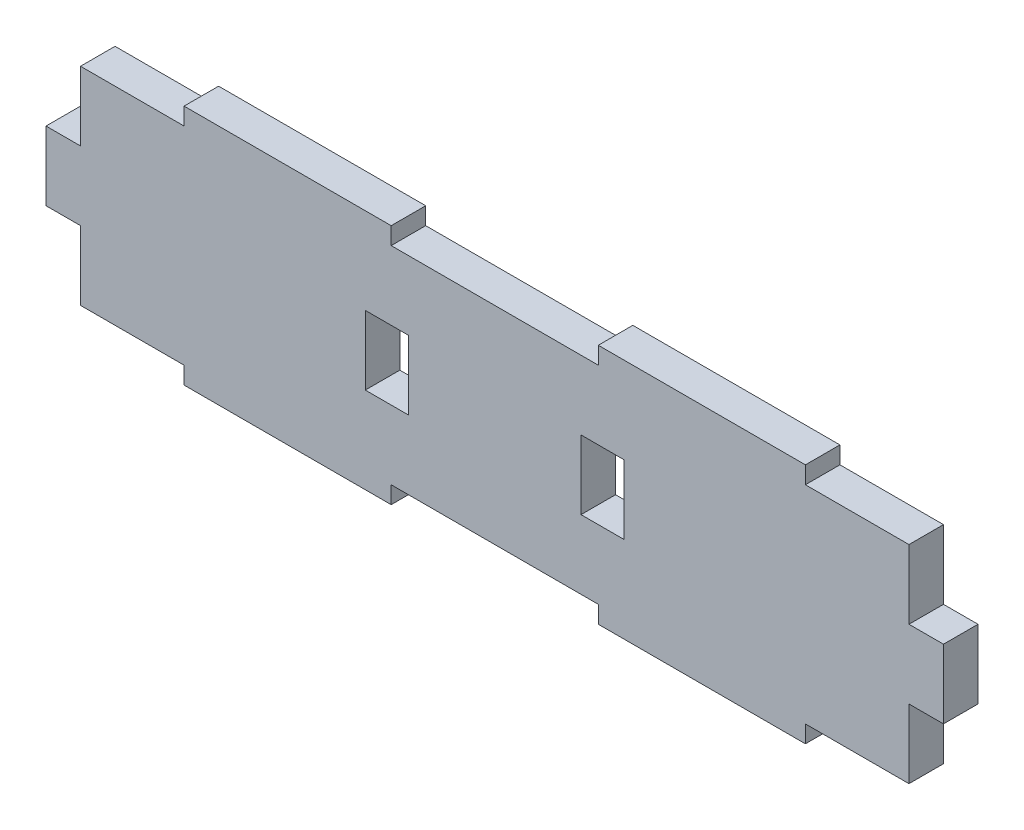
SolidWorks part; units mm, degrees
material "7050-T73510"
ref_plane "Front Plane" through (0, 0, 0) normal (0, 0, 1) x (1, 0, 0)
ref_plane "Top Plane" through (0, 0, 0) normal (0, 1, 0) x (1, 0, 0)
ref_plane "Right Plane" through (0, 0, 0) normal (1, 0, 0) x (0, 0, -1)
sketch "Sketch1" plane through (0, 0, 0) normal (0, 0, 1) x (1, 0, 0)
  line L1 (-165.1, -38.1) -> (165.1, -38.1)
  line L2 (-165.1, -38.1) -> (-165.1, 38.1)
  line L3 (-165.1, 38.1) -> (165.1, 38.1)
  line L4 (165.1, -38.1) -> (165.1, 38.1)
  line L5 (-165.1, -38.1) -> (165.1, 38.1) construction
  line L6 (-165.1, 38.1) -> (165.1, -38.1) construction
  point P0 (0, 0)
  dimension "D1" = 330.2
  dimension "D2" = 76.2
extrude "Boss-Extrude1" add sketch "Sketch1" along normal blind 12.7 contours L1 L3 region at (0, 0, 0)
sketch "Sketch2" plane through (0, 0, 12.7) normal (0, 0, 1) x (1, 0, 0)
  line L0 (-165.1, -38.1) -> (165.1, -38.1) construction
  line L1 (-38.1, -38.1) -> (-114.3, -38.1)
  line L2 (-38.1, -38.1) -> (-38.1, -44.45)
  line L3 (-38.1, -44.45) -> (-114.3, -44.45)
  line L4 (-114.3, -38.1) -> (-114.3, -44.45)
  line L5 (0, -55) -> (0, 55) construction
  line L6 (38.1, -44.45) -> (114.3, -44.45)
  line L7 (114.3, -38.1) -> (114.3, -44.45)
  line L8 (38.1, -38.1) -> (114.3, -38.1)
  line L9 (38.1, -38.1) -> (38.1, -44.45)
  line L10 (55, 0) -> (-55, 0) construction
  line L11 (38.1, 38.1) -> (38.1, 44.45)
  line L12 (38.1, 38.1) -> (114.3, 38.1)
  line L13 (114.3, 38.1) -> (114.3, 44.45)
  line L14 (38.1, 44.45) -> (114.3, 44.45)
  line L15 (-38.1, 44.45) -> (-114.3, 44.45)
  line L16 (-114.3, 38.1) -> (-114.3, 44.45)
  line L17 (-38.1, 38.1) -> (-114.3, 38.1)
  line L18 (-38.1, 38.1) -> (-38.1, 44.45)
  point P12 (-38.1, -41.275)
  dimension "D1" = 76.2
  dimension "D2" = 6.35
  dimension "D3" = 76.2
extrude "Boss-Extrude2" add sketch "Sketch2" against normal blind 12.7
sketch "Sketch3" plane through (0, 0, 12.7) normal (0, 0, 1) x (1, 0, 0)
  line L0 (6.985, 0) -> (-6.985, 0) construction
  line L1 (-165.1, -38.1) -> (-152.4, -38.1)
  line L2 (-165.1, -38.1) -> (-165.1, -12.7)
  line L3 (-165.1, -12.7) -> (-152.4, -12.7)
  line L4 (-152.4, -38.1) -> (-152.4, -12.7)
  line L6 (-165.1, 12.7) -> (-152.4, 12.7)
  line L7 (-152.4, 38.1) -> (-152.4, 12.7)
  line L8 (-165.1, 38.1) -> (-152.4, 38.1)
  line L9 (-165.1, 38.1) -> (-165.1, 12.7)
  line L10 (0, -6.985) -> (0, 6.985) construction
  line L11 (165.1, 38.1) -> (165.1, 12.7)
  line L12 (165.1, 38.1) -> (152.4, 38.1)
  line L13 (152.4, 38.1) -> (152.4, 12.7)
  line L14 (165.1, 12.7) -> (152.4, 12.7)
  line L15 (165.1, -12.7) -> (152.4, -12.7)
  line L16 (152.4, -38.1) -> (152.4, -12.7)
  line L17 (165.1, -38.1) -> (152.4, -38.1)
  line L18 (165.1, -38.1) -> (165.1, -12.7)
  line L19 (31.75, 12.7) -> (47.625, 12.7)
  line L20 (31.75, 12.7) -> (31.75, -12.7)
  line L21 (31.75, -12.7) -> (47.625, -12.7)
  line L22 (47.625, 12.7) -> (47.625, -12.7)
  line L23 (-38.1, -38.1) -> (38.1, -38.1) construction
  line L24 (-31.75, -12.7) -> (-47.625, -12.7)
  line L25 (-47.625, 12.7) -> (-47.625, -12.7)
  line L26 (-31.75, 12.7) -> (-47.625, 12.7)
  line L27 (-31.75, 12.7) -> (-31.75, -12.7)
  line L28 (-38.1, 38.1) -> (38.1, 38.1) construction
  dimension "D1" = 25.4
  dimension "D2" = 12.7
  dimension "D3" = 63.5
  dimension "D4" = 15.875
  dimension "D5" = 25.4
  dimension "D6" = 25.4
extrude "Cut-Extrude1" cut sketch "Sketch3" against normal through all
